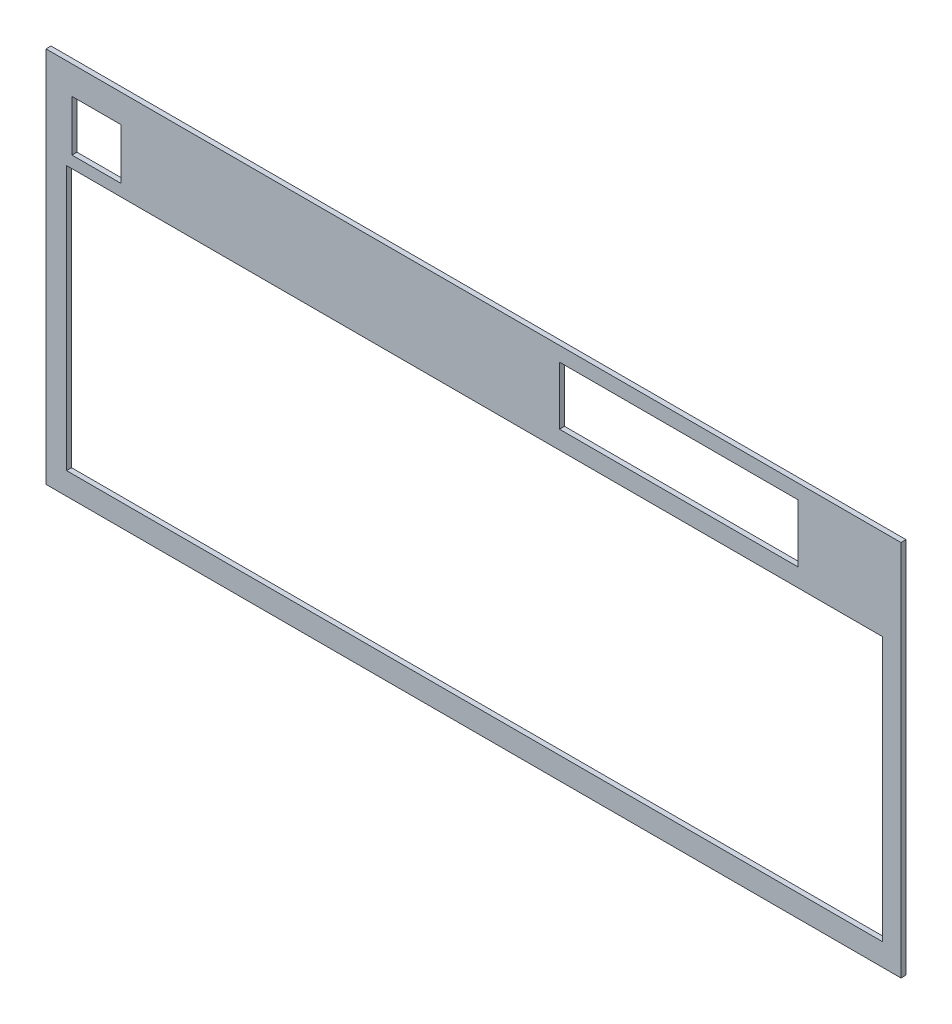
SolidWorks part; units mm, degrees
ref_plane "Front Plane" through (0, 0, 0) normal (0, 0, 1) x (1, 0, 0)
ref_plane "Top Plane" through (0, 0, 0) normal (0, 1, 0) x (1, 0, 0)
ref_plane "Right Plane" through (0, 0, 0) normal (1, 0, 0) x (0, 0, -1)
sketch "Sketch1" plane through (0, 0, 0) normal (0, 0, 1) x (1, 0, 0)
  line L0 (-65.3579, 80.1382) -> (268.6427, 80.1382)
  line L6 (268.6427, -69.8367) -> (-68.3452, -69.8367)
  line L7 (-68.3452, -69.8367) -> (-68.3452, 80.1382)
  line L8 (-68.3452, 80.1382) -> (-65.3579, 80.1382)
  line L9 (268.6427, -69.8367) -> (271.63, -69.8367)
  line L10 (271.63, -69.8367) -> (271.63, 80.1382)
  line L11 (268.6427, 80.1382) -> (271.63, 80.1382)
  line L13 (-58.0282, 68.9533) -> (-38.5345, 68.9533)
  line L14 (-58.0282, 68.9533) -> (-58.0282, 48.7377)
  line L15 (-58.0282, 48.7377) -> (-38.5345, 48.7377)
  line L16 (-38.5345, 68.9533) -> (-38.5345, 48.7377)
  line L17 (-60.1941, 44.0447) -> (264.3023, 44.0447)
  line L18 (-60.1941, 44.0447) -> (-60.1941, -61.0045)
  line L19 (-60.1941, -61.0045) -> (264.3023, -61.0045)
  line L20 (264.3023, 44.0447) -> (264.3023, -61.0045)
  line L21 (135.8256, 74.3682) -> (230.767, 74.3682)
  line L22 (135.8256, 74.3682) -> (135.8256, 51.2646)
  line L23 (135.8256, 51.2646) -> (230.767, 51.2646)
  line L24 (230.767, 74.3682) -> (230.767, 51.2646)
extrude "Boss-Extrude1" add sketch "Sketch1" along normal blind 2
